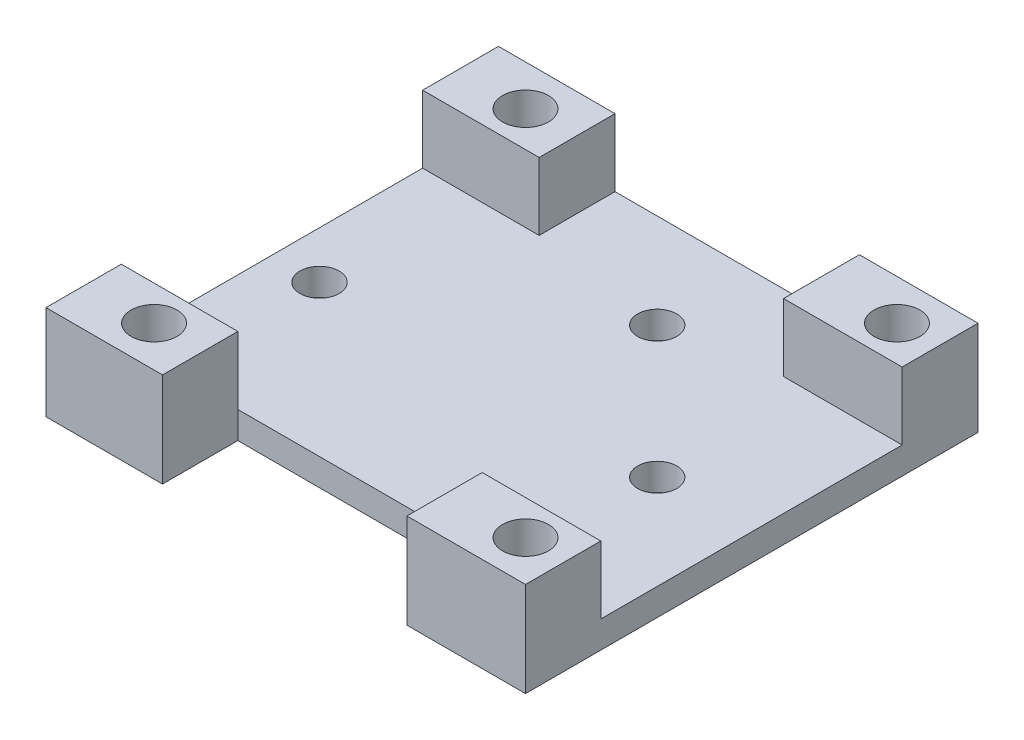
SolidWorks part; units mm, degrees
ref_plane "Front Plane" through (0, 0, 0) normal (0, 0, 1) x (1, 0, 0)
ref_plane "Top Plane" through (0, 0, 0) normal (0, 1, 0) x (1, 0, 0)
ref_plane "Right Plane" through (0, 0, 0) normal (1, 0, 0) x (0, 0, -1)
sketch "Sketch1" plane through (0, 0, 0) normal (0, 1, 0) x (1, 0, 0)
  line L1 (-20, 16.75) -> (20, 16.75)
  line L2 (-20, 16.75) -> (-20, -16.75)
  line L3 (-20, -16.75) -> (20, -16.75)
  line L4 (20, 16.75) -> (20, -16.75)
  line L5 (-20, 16.75) -> (20, -16.75) construction
  line L6 (-20, -16.75) -> (20, 16.75) construction
  point P0 (0, 0)
  dimension "D1" = 40
  dimension "D2" = 33.5
extrude "Boss-Extrude1" add sketch "Sketch1" along normal blind 7
hole_wizard "M3 Clearance Hole1" positions "3DSketch1" profile "Sketch2" hole size "M3" standard "ANSI Metric" end condition through all
sketch3d "3DSketch1"
  line L0 (-20, 7, -16.75) -> (-20, 7, 16.75) construction
  line L1 (-20, 7, 16.75) -> (20, 7, 16.75) construction
  line L2 (20, 7, -16.75) -> (-20, 7, -16.75) construction
  line L3 (20, 7, 16.75) -> (20, 7, -16.75) construction
  point P0 (-10.5, 7, 13.75)
  point P2 (17, 7, -13.75)
  dimension "D1" = 9.5
  dimension "D2" = 3
  dimension "D3" = 3
  dimension "D4" = 3
  dimension "D5" = 38.8909
sketch "Sketch2" plane through (-10.5, 7, 13.75) normal (1, 0, 0) x (0, 0, 1)
  line L0 (0, 0) -> (0, 7)
  line L1 (0, 7) -> (1.7, 7)
  line L2 (1.7, 7) -> (1.7, 0)
  line L5 (1.7, 0) -> (0, 0)
  line L11 (0, -6.35) -> (0, 107.95) construction
  dimension "Thru Hole Dia." = 3.4
  dimension "Thru Hole Depth" = 7
sketch "Sketch3" plane through (0, 7, 0) normal (0, 1, 0) x (1, 0, 0)
  line L0 (-20, -11.1763) -> (20, -11.1763)
  line L1 (-20, 16.75) -> (11.2193, 16.75)
  line L2 (-20, 16.75) -> (-20, -11.1763)
  line L4 (11.2193, 16.75) -> (11.2193, -11.1763)
  line L6 (-6.8726, -11.1763) -> (-6.8726, -16.75)
  line L7 (-6.8726, -16.75) -> (20, -16.75)
  line L8 (20, -11.1763) -> (20, -16.75)
  line L9 (11.2193, 11.1333) -> (20, 11.1333)
  line L12 (20, 11.1333) -> (20, -11.1763)
sketch "Sketch4" plane through (0, 7, 0) normal (0, 1, 0) x (1, 0, 0)
  line L1 (-20, 16.75) -> (11.2193, 16.75)
  line L2 (-20, 16.75) -> (-20, -11.1763)
  line L3 (-20, -11.1763) -> (11.2193, -11.1763)
  line L4 (11.2193, 16.75) -> (11.2193, -11.1763)
extrude "Cut-Extrude1" cut sketch "Sketch4" against normal blind 5
sketch "Sketch5" plane through (0, 7, 0) normal (0, 1, 0) x (1, 0, 0)
  line L1 (11.2193, 11.1333) -> (20, 11.1333)
  line L2 (11.2193, 11.1333) -> (11.2193, -11.1763)
  line L3 (11.2193, -11.1763) -> (20, -11.1763)
  line L4 (20, 11.1333) -> (20, -11.1763)
extrude "Cut-Extrude2" cut sketch "Sketch5" against normal blind 5
hole_wizard "M2.5 Clearance Hole2" positions "3DSketch3" profile "Sketch8" hole size "M2.5" standard "ANSI Metric" end condition through all
sketch3d "3DSketch3"
  line L5 (-20, 2, -16.75) -> (-20, 2, 11.1763) construction
  line L8 (11.2193, 2, -16.75) -> (-20, 2, -16.75) construction
  line L9 (20, 2, 11.1763) -> (20, 2, -11.1333) construction
  point P0 (-12, 2, 0)
  point P2 (13, 2, 0)
  point P4 (3.25, 2, -9.75)
  dimension "D1" = 8
  dimension "D7" = 25
  dimension "D2" = 16.75
  dimension "D8" = 32
  dimension "D3" = 7
  dimension "D4" = 7
  dimension "D5" = 16.75
  dimension "D6" = 16.75
sketch "Sketch8" plane through (-12, 2, 0) normal (1, 0, 0) x (0, 0, 1)
  line L0 (0, 0) -> (0, 2)
  line L1 (0, 2) -> (1.45, 2)
  line L2 (1.45, 2) -> (1.45, 0)
  line L5 (1.45, 0) -> (0, 0)
  line L11 (0, -6.35) -> (0, 107.95) construction
  dimension "Thru Hole Dia." = 2.9
  dimension "Thru Hole Depth" = 2
sketch "Sketch12" plane through (0, 7, 0) normal (0, 1, 0) x (1, 0, 0)
  line L1 (-6.8726, -11.1763) -> (20, -11.1763)
  line L2 (-6.8726, -11.1763) -> (-6.8726, -16.75)
  line L3 (-6.8726, -16.75) -> (20, -16.75)
  line L4 (20, -11.1763) -> (20, -16.75)
extrude "Cut-Extrude4" cut sketch "Sketch12" against normal through all
sketch "Sketch13" plane through (0, 0, 0) normal (0, -1, 0) x (1, 0, 0)
  line L1 (11.2193, 11.1763) -> (20, 11.1763)
  line L2 (11.2193, 11.1763) -> (11.2193, 16.75)
  line L3 (11.2193, 16.75) -> (20, 16.75)
  line L4 (20, 11.1763) -> (20, 16.75)
extrude "Boss-Extrude2" add sketch "Sketch13" against normal up to vertex (7 mm away) up to point (-6.8726, 7, 16.75)
sketch "Sketch14" plane through (0, 2, 0) normal (0, 1, 0) x (1, 0, 0)
  line L0 (-20, 16.75) -> (11.2193, 16.75) construction
  line L1 (-6.8726, 16.75) -> (-20, 16.75)
  line L2 (-6.8726, 16.75) -> (-6.8726, 11.1333)
  line L3 (-6.8726, 11.1333) -> (-20, 11.1333)
  line L4 (-20, 16.75) -> (-20, 11.1333)
  line L6 (11.2193, 11.1333) -> (20, 11.1333) construction
  line L7 (-20, 16.75) -> (-20, -11.1763) construction
  dimension "D1" = 0
  dimension "D2" = 5.6167
  dimension "D3" = 0
extrude "Boss-Extrude3" add sketch "Sketch14" along normal up to vertex (5 mm away) up to point (11.2193, 7, -11.1333)
hole_wizard "M3 Clearance Hole2" positions "Sketch16" profile "Sketch15" hole size "M3" standard "ANSI Metric" end condition through all
sketch "Sketch16" plane through (0, 7, 0) normal (0, 1, 0) x (1, 0, 0)
  line L0 (-20, 16.75) -> (-20, -11.1763) construction
  line L1 (-20, 16.75) -> (11.2193, 16.75) construction
  line L2 (20, -11.1763) -> (20, -16.75) construction
  line L3 (-6.8726, -16.75) -> (20, -16.75) construction
  point P0 (-10.5, 13.75)
  point P2 (17, -13.75)
  dimension "D1" = 9.5
  dimension "D2" = 3
  dimension "D3" = 3
  dimension "D4" = 3
  dimension "D5" = 38.8909
sketch "Sketch15" plane through (-10.5, 7, -13.75) normal (1, 0, 0) x (0, 0, 1)
  line L0 (0, 0) -> (0, 7)
  line L1 (0, 7) -> (1.7, 7)
  line L2 (1.7, 7) -> (1.7, 0)
  line L5 (1.7, 0) -> (0, 0)
  line L11 (0, -6.35) -> (0, 107.95) construction
  dimension "Thru Hole Dia." = 3.4
  dimension "Thru Hole Depth" = 7
sketch "Sketch17" plane through (0, 7, 0) normal (0, 1, 0) x (1, 0, 0)
  line L0 (-20, -16.75) -> (-6.8726, -16.75) construction
  line L1 (-20, 16.75) -> (-15.5, 16.75)
  line L2 (-20, 16.75) -> (-20, -16.75)
  line L3 (-20, -16.75) -> (-15.5, -16.75)
  line L4 (-15.5, 16.75) -> (-15.5, -16.75)
  dimension "D1" = 4.5
extrude "Cut-Extrude5" cut sketch "Sketch17" against normal through all
